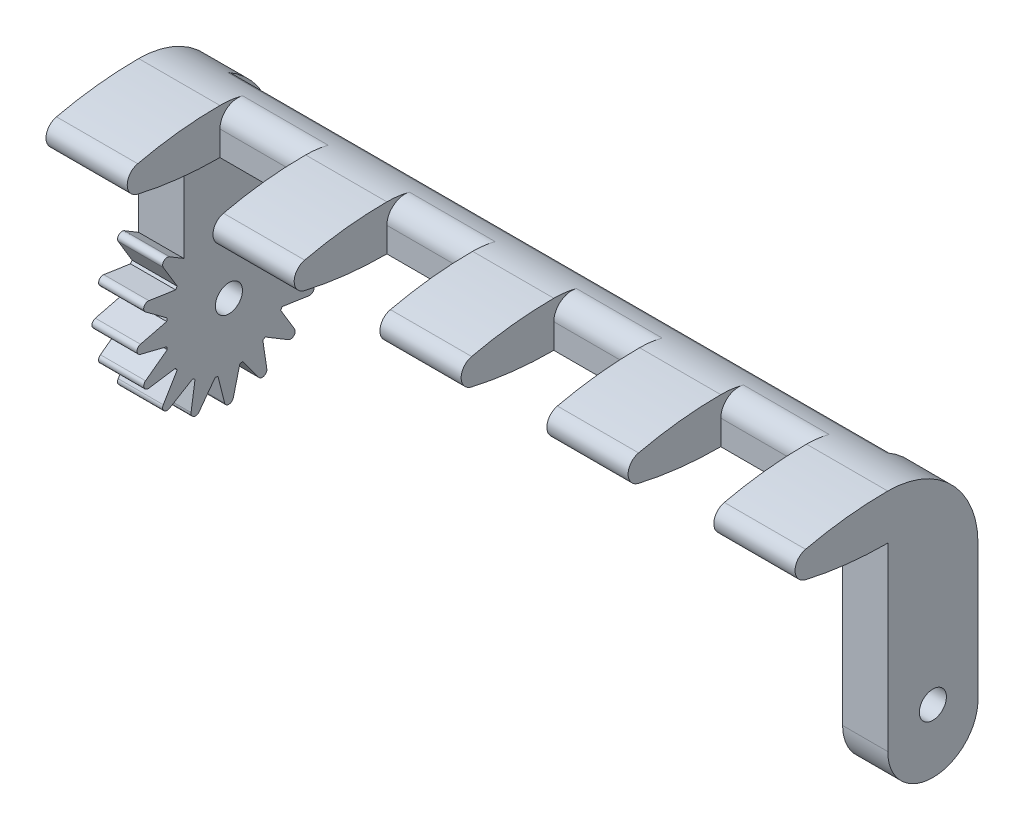
SolidWorks part; units mm, degrees
ref_plane "Plan de face" through (0, 0, 0) normal (0, 0, 1) x (1, 0, 0)
ref_plane "Plan de dessus" through (0, 0, 0) normal (0, 1, 0) x (1, 0, 0)
ref_plane "Plan de droite" through (0, 0, 0) normal (1, 0, 0) x (0, 0, -1)
sketch "Esquisse1" plane through (0, 0, 0) normal (0, 0, 1) x (1, 0, 0)
  line L0 (-36.5, 10) -> (36.5, 10)
  line L1 (-41.5, 15) -> (41.5, 15)
  line L2 (-41.5, 15) -> (-41.5, -15)
  line L3 (-41.5, -15) -> (-36.5, -15)
  line L4 (41.5, 15) -> (41.5, -15)
  line L5 (-41.5, 15) -> (41.5, -15) construction
  line L6 (-41.5, -15) -> (41.5, 15) construction
  line L7 (36.5, 10) -> (36.5, -10)
  line L8 (-36.5, -10) -> (36.5, -10) construction
  line L9 (-36.5, 10) -> (-36.5, -10)
  line L10 (-36.5, -10) -> (-36.5, -15)
  line L11 (36.5, -10) -> (36.5, -15)
  line L12 (36.5, -15) -> (41.5, -15)
  line L13 (-41.5, -15) -> (41.5, -15) construction
  point P0 (0, 0)
  dimension "D1" = 83
  dimension "D2" = 30
  dimension "D3" = 5
extrude "Boss.-Extru.1" add sketch "Esquisse1" along normal blind 10
sketch "Esquisse2" plane through (-41.5, 0, 0) normal (-1, 0, 0) x (0, 0, 1)
  line L0 (10, 15) -> (0, 15) construction
  line L1 (10, 15) -> (10, -15) construction
  line L2 (24, 12.5) -> (10, 12.5) construction
  line L3 (10, 10) -> (10, 15)
  line L4 (10, 10) -> (0, 10) construction
  line L5 (10, 10) -> (0, 10) construction
  arc A0 (10, 15) -> (24, 12.5) centre (10, -25.45) cw
  arc A1 (10, 10) -> (24, 12.5) centre (10, 50.45) ccw
  point P13 (0, 0)
  dimension "D2" = 14
extrude "Boss.-Extru.2" add sketch "Esquisse2" against normal blind 9
fillet "Congé1" radius 1.5 1 edges at (-37, 12.5, 24)
pattern_linear "Répétition linéaire1" count 5 spacing 18.5 along (1, 0, 0) of "Boss.-Extru.2", "Congé1"
sketch "Esquisse4" plane through (-36.5, 0, 0) normal (1, 0, 0) x (0, 0, -1)
  line L0 (-10, -8) -> (0, -8) construction
  line L4 (0, -15) -> (0, 10)
  line L5 (0, 10) -> (-10, 10)
  line L6 (-10, 10) -> (-10, -15)
  line L7 (-10, -15) -> (0, -15)
  line L8 (0, -15) -> (0, 10)
  line L9 (0, 10) -> (-10, 10)
  line L10 (-10, 10) -> (-10, -15) construction
  line L11 (-10, -15) -> (0, -15)
  circle A0 centre (-5, -8) radius 1.5
  dimension "D3" = 3
  dimension "D2" = 7
  dimension "D1" = 0
extrude "Enlèv. mat.-Extru.1" cut sketch "Esquisse4" against normal through all and the other way through all contours A0 region at (-36.5, -8, 5)
fillet "Congé2" 2 edges at (-39, -15, 0) (-39, -15, 10) type full round first side face at (0, -1.25, 0) second side face at (-39, -2.5, 10) middle face at (-39, -15, 5)
fillet "Congé3" 2 edges at (39, -15, 0) (39, -15, 10) type full round first side face at (0, 0, 0) second side face at (39, -2.5, 10) middle face at (39, -15, 5)
fillet "Congé4" radius 10 1 edges at (0, 15, 0)
sketch "Esquisse5" plane through (-36.5, 0, 0) normal (1, 0, 0) x (0, 0, -1)
  line L0 (-12, -8) -> (2, -8) construction
  line L1 (-14.8004, -8.4851) -> (-11.8947, -9.2096)
  line L2 (-14.8004, -7.5149) -> (-11.8947, -6.7904)
  line L3 (-14.24, -4.6978) -> (-11.8328, -6.479)
  line L4 (-13.8687, -3.8013) -> (-10.907, -4.244)
  line L5 (-12.2729, -1.4132) -> (-10.7306, -3.98)
  line L6 (-11.5868, -0.7271) -> (-9.02, -2.2694)
  line L7 (-9.1987, 0.8687) -> (-8.756, -2.093)
  line L8 (-8.3022, 1.24) -> (-6.521, -1.1672)
  line L9 (-5.4851, 1.8004) -> (-6.2096, -1.1053)
  line L10 (-4.5149, 1.8004) -> (-3.7904, -1.1053)
  line L11 (-1.6978, 1.24) -> (-3.479, -1.1672)
  line L12 (-0.8013, 0.8687) -> (-1.244, -2.093)
  line L13 (1.5868, -0.7271) -> (-0.98, -2.2694)
  line L14 (2.2729, -1.4132) -> (0.7306, -3.98)
  line L15 (3.8687, -3.8013) -> (0.907, -4.244)
  line L16 (4.24, -4.6978) -> (1.8328, -6.479)
  line L17 (4.8004, -7.5149) -> (1.8947, -6.7904)
  line L18 (4.8004, -8.4851) -> (1.8947, -9.2096)
  line L19 (4.24, -11.3022) -> (1.8328, -9.521)
  line L20 (3.8687, -12.1987) -> (0.907, -11.756)
  line L21 (2.2729, -14.5868) -> (0.7306, -12.02)
  line L22 (1.5868, -15.2729) -> (-0.98, -13.7306)
  line L23 (-0.8013, -16.8687) -> (-1.244, -13.907)
  line L24 (-1.6978, -17.24) -> (-3.479, -14.8328)
  line L25 (-4.5149, -17.8004) -> (-3.7904, -14.8947)
  line L26 (-5.4851, -17.8004) -> (-6.2096, -14.8947)
  line L27 (-8.3022, -17.24) -> (-6.521, -14.8328)
  line L28 (-9.1987, -16.8687) -> (-8.756, -13.907)
  line L29 (-11.5868, -15.2729) -> (-9.02, -13.7306)
  line L30 (-12.2729, -14.5868) -> (-10.7306, -12.02)
  line L31 (-13.8687, -12.1987) -> (-10.907, -11.756)
  line L32 (-14.24, -11.3022) -> (-11.8328, -9.521)
  arc A0 (-10.907, -11.756) -> (-10.7306, -12.02) centre (-5, -8) ccw
  arc A1 (-10, -10) -> (0, -10) centre (-5, -10) ccw construction
  arc A2 (-14.8004, -8.4851) -> (-14.8004, -7.5149) centre (-14.6794, -8) cw
  arc A3 (-14.24, -4.6978) -> (-13.8687, -3.8013) centre (-13.9426, -4.2959) cw
  arc A4 (-12.2729, -1.4132) -> (-11.5868, -0.7271) centre (-11.8444, -1.1556) cw
  arc A5 (-9.1987, 0.8687) -> (-8.3022, 1.24) centre (-8.7041, 0.9426) cw
  arc A6 (-5.4851, 1.8004) -> (-4.5149, 1.8004) centre (-5, 1.6794) cw
  arc A7 (-1.6978, 1.24) -> (-0.8013, 0.8687) centre (-1.2959, 0.9426) cw
  arc A8 (1.5868, -0.7271) -> (2.2729, -1.4132) centre (1.8444, -1.1556) cw
  arc A9 (3.8687, -3.8013) -> (4.24, -4.6978) centre (3.9426, -4.2959) cw
  arc A10 (4.8004, -7.5149) -> (4.8004, -8.4851) centre (4.6794, -8) cw
  arc A11 (4.24, -11.3022) -> (3.8687, -12.1987) centre (3.9426, -11.7041) cw
  arc A12 (2.2729, -14.5868) -> (1.5868, -15.2729) centre (1.8444, -14.8444) cw
  arc A13 (-0.8013, -16.8687) -> (-1.6978, -17.24) centre (-1.2959, -16.9426) cw
  arc A14 (-4.5149, -17.8004) -> (-5.4851, -17.8004) centre (-5, -17.6794) cw
  arc A15 (-8.3022, -17.24) -> (-9.1987, -16.8687) centre (-8.7041, -16.9426) cw
  arc A16 (-11.5868, -15.2729) -> (-12.2729, -14.5868) centre (-11.8444, -14.8444) cw
  arc A17 (-13.8687, -12.1987) -> (-14.24, -11.3022) centre (-13.9426, -11.7041) cw
  arc A18 (-9.02, -13.7306) -> (-8.756, -13.907) centre (-5, -8) ccw
  arc A19 (-6.521, -14.8328) -> (-6.2096, -14.8947) centre (-5, -8) ccw
  arc A20 (-3.7904, -14.8947) -> (-3.479, -14.8328) centre (-5, -8) ccw
  arc A21 (-1.244, -13.907) -> (-0.98, -13.7306) centre (-5, -8) ccw
  arc A22 (0.7306, -12.02) -> (0.907, -11.756) centre (-5, -8) ccw
  arc A23 (1.8328, -9.521) -> (1.8947, -9.2096) centre (-5, -8) ccw
  arc A24 (1.8947, -6.7904) -> (1.8328, -6.479) centre (-5, -8) ccw
  arc A25 (0.907, -4.244) -> (0.7306, -3.98) centre (-5, -8) ccw
  arc A26 (-0.98, -2.2694) -> (-1.244, -2.093) centre (-5, -8) ccw
  arc A27 (-3.479, -1.1672) -> (-3.7904, -1.1053) centre (-5, -8) ccw
  arc A28 (-6.2096, -1.1053) -> (-6.521, -1.1672) centre (-5, -8) ccw
  arc A29 (-8.756, -2.093) -> (-9.02, -2.2694) centre (-5, -8) ccw
  arc A30 (-10.7306, -3.98) -> (-10.907, -4.244) centre (-5, -8) ccw
  arc A31 (-11.8328, -6.479) -> (-11.8947, -6.7904) centre (-5, -8) ccw
  arc A32 (-11.8947, -9.2096) -> (-11.8328, -9.521) centre (-5, -8) ccw
  circle A33 centre (-5, -8) radius 1.5 construction
  circle A34 centre (-5, -8) radius 1.5
  point P14 (-16.7462, -8)
  point P92 (-5, -8)
  dimension "D3" = 0.5
  dimension "D1" = 14
  dimension "D2" = 5
  dimension "D4" = 16
extrude "Boss.-Extru.3" add sketch "Esquisse5" against normal through all
fillet "Congé7" radius 2 1 edges at (0, 10, 1.3397)
fillet "Congé8" radius 2 4 edges at (27.75, 15, 10) (9.25, 15, 10) (-9.25, 15, 10) (-27.75, 15, 10)
